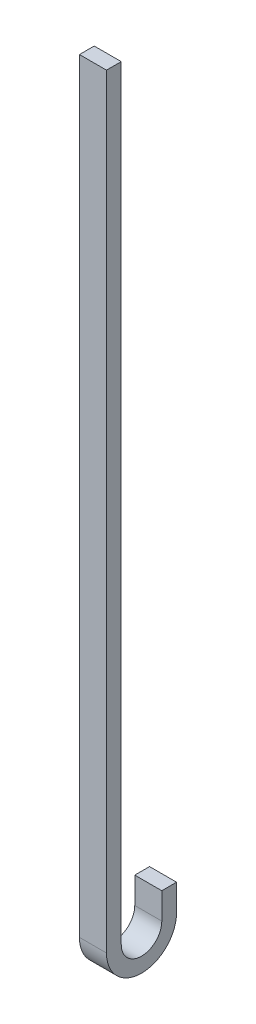
SolidWorks part; units mm, degrees
ref_plane "Front" through (0, 0, 0) normal (0, 0, 1) x (1, 0, 0)
ref_plane "Top" through (0, 0, 0) normal (0, 1, 0) x (1, 0, 0)
ref_plane "Right" through (0, 0, 0) normal (1, 0, 0) x (0, 0, -1)
sketch "Sketch1" plane through (0, 0, 0) normal (1, 0, 0) x (0, 0, -1)
  line L0 (0, 0) -> (0, -775.9925)
  line L1 (71.12, -775.9925) -> (71.12, -749.3)
  line L2 (14.986, 0) -> (14.986, -775.9925)
  line L3 (56.134, -775.9925) -> (56.134, -749.3)
  line L4 (0, 0) -> (14.986, 0)
  line L5 (56.134, -749.3) -> (71.12, -749.3)
  line L7 (82.55, -901.7) -> (-6.35, -901.7) construction
  arc A0 (0, -775.9925) -> (71.12, -775.9925) centre (35.56, -775.9925) ccw
  arc A1 (14.986, -775.9925) -> (56.134, -775.9925) centre (35.56, -775.9925) ccw
  dimension "D1" = 914.4
  dimension "D2" = 71.12
  dimension "D4" = 41.148
  dimension "D5" = 152.4
  dimension "D3" = 14.986
extrude "Boss-Extrude1" add sketch "Sketch1" along normal blind 27.432
